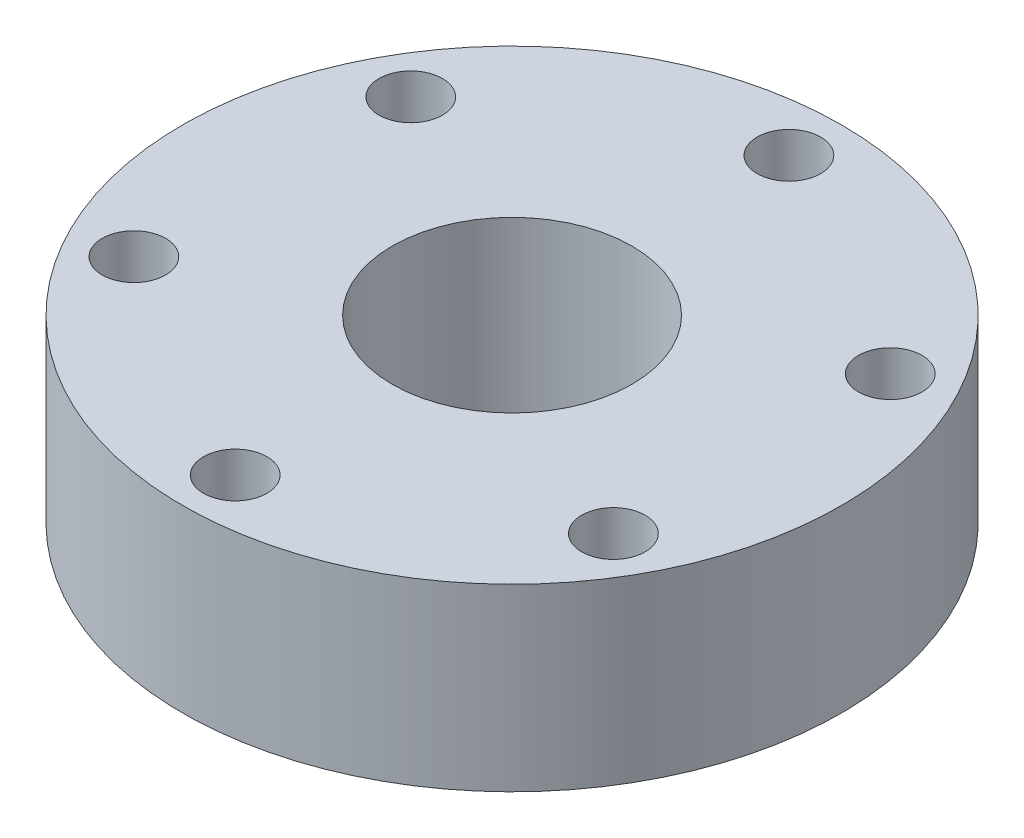
SolidWorks part; units mm, degrees
ref_plane "Front Plane" through (0, 0, 0) normal (0, 0, 1) x (1, 0, 0)
ref_plane "Top Plane" through (0, 0, 0) normal (0, 1, 0) x (1, 0, 0)
ref_plane "Right Plane" through (0, 0, 0) normal (1, 0, 0) x (0, 0, -1)
sketch "Sketch1" plane through (0, 0, 0) normal (0, 1, 0) x (1, 0, 0)
  circle A0 centre (0, 0) radius 34.925
  dimension "D1" = 69.85
extrude "Extrude1" add sketch "Sketch1" along normal blind 19.05
sketch "Sketch2" plane through (0, 0, 0) normal (0, 1, 0) x (1, 0, 0)
  circle A0 centre (0, 0) radius 12.7
  dimension "D1" = 25.4
extrude "Cut-Extrude1" cut sketch "Sketch2" along normal through all
sketch "Sketch3" plane through (0, 0, 0) normal (0, 1, 0) x (1, 0, 0)
  circle A0 centre (0, 29.337) radius 3.3655
  dimension "D1" = 6.731
  dimension "D2" = 29.337
extrude "Cut-Extrude2" cut sketch "Sketch3" along normal through all
ref_axis "Axis1" through (0, 35.8582, 0) along (0, -1, 0)
pattern_circular "CirPattern1" count 6 over 360 about axis through (0, 35.8582, 0) along (0, -1, 0) of "Cut-Extrude2"
sketch "Sketch4" plane through (0, 0, 0) normal (0, 1, 0) x (1, 0, 0)
  line L0 (0, 0) -> (0, 16.8619)
ref_plane "Plane1" through (0, 0, 0) normal (0, -1, 0) x (1, 0, 0)
sketch "Sketch5" plane through (0, 0, 0) normal (0, -1, 0) x (1, 0, 0)
  circle A0 centre (0, 0) radius 4.7625
  dimension "D1" = 9.525
